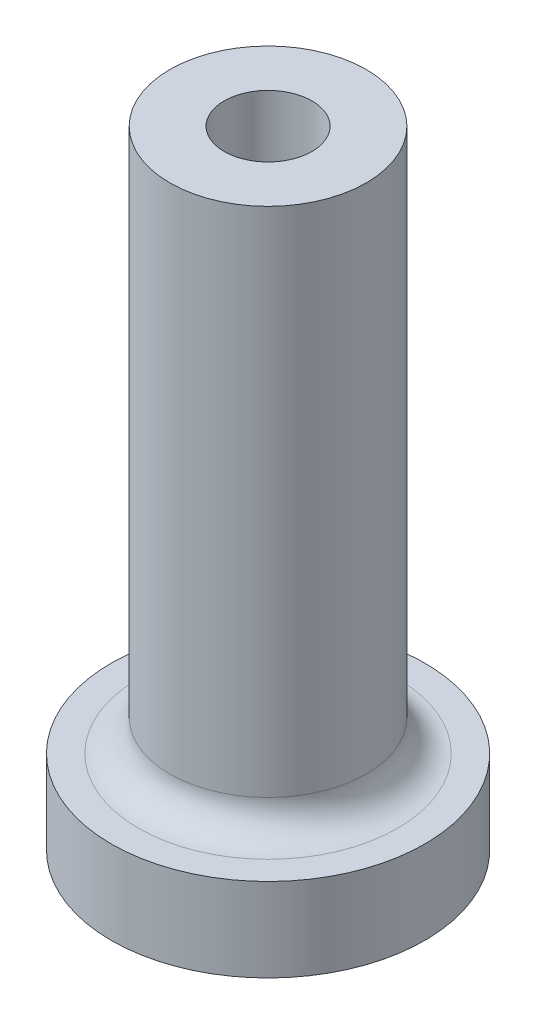
SolidWorks part; units mm, degrees
ref_plane "Front Plane" through (0, 0, 0) normal (0, 0, 1) x (1, 0, 0)
ref_plane "Top Plane" through (0, 0, 0) normal (0, 1, 0) x (1, 0, 0)
ref_plane "Right Plane" through (0, 0, 0) normal (1, 0, 0) x (0, 0, -1)
sketch "Sketch1" plane through (0, 0, 0) normal (0, 1, 0) x (1, 0, 0)
  circle A0 centre (0, 0) radius 7.5
  circle A1 centre (0, 0) radius 4.7
  circle A2 centre (0, 0) radius 2.1
  dimension "D1" = 4.2
  dimension "D2" = 9.4
  dimension "D3" = 15
extrude "Boss-Extrude1" add sketch "Sketch1" along normal blind 4 contours A2 | A1 A2 | A0 A1 region at (-7.2879, 0, 0) region at (-4.5671, 0, 0) region at (0, 0, 0)
extrude "Boss-Extrude2" add sketch "Sketch1<3>" along normal blind 26 from surface contours A1 A2 | A2 region at (-4.5671, 0, 0) region at (0, 0, 0) starting at face at (0, 4, 7.5)
sketch "Sketch1<3>" plane through (0, 0, 0) normal (0, 1, 0) x (1, 0, 0) same geometry as "Sketch1"
extrude "Cut-Extrude1" cut sketch "Sketch1<4>" against normal blind 10 from surface contours A2 region at (0, 0, 0) starting at face at (0, 30, 4.7)
sketch "Sketch1<4>" plane through (0, 0, 0) normal (0, 1, 0) x (1, 0, 0) same geometry as "Sketch1"
fillet "Fillet1" radius 1.5 1 edges at (0, 4, 4.7)
